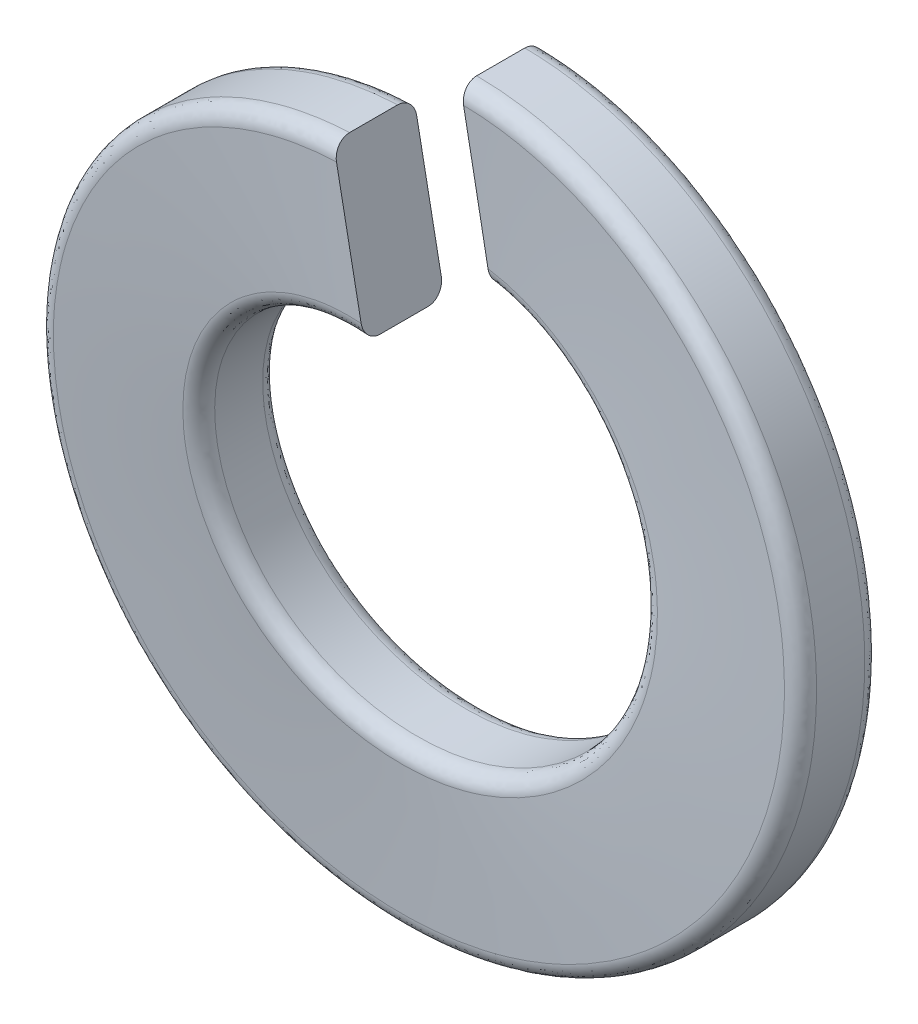
SolidWorks part; units mm, degrees
material "Plain Carbon Steel"
ref_plane "Front Plane" through (0, 0, 0) normal (0, 0, 1) x (1, 0, 0)
ref_plane "Top Plane" through (0, 0, 0) normal (0, 1, 0) x (1, 0, 0)
ref_plane "Right Plane" through (0, 0, 0) normal (1, 0, 0) x (0, 0, -1)
sketch "Sketch1" plane through (0, 0, 0) normal (0, 0, 1) x (1, 0, 0)
  line L0 (0, -2.2) -> (0, 2.2) construction
  line L1 (-0.096, 2.1979) -> (0.0978, 1.196) construction
  line L2 (0, 0) -> (-0.6, -1.0392) construction
  line L3 (0, 1.2) -> (-0.1917, 2.1916) construction
  line L4 (0, 0) -> (-0.1917, 2.1916) construction
  line L5 (-0.096, 2.1979) -> (0, 0) construction
  circle A0 centre (0, 0) radius 2.2 construction
  circle A1 centre (0, 0) radius 1.2 construction
  point P6 (0, -1.2)
  dimension "ID" = 2.4
  dimension "OD" = 4.4
  dimension "D2" = 5
  dimension "D1" = 30
  dimension "D3" = 2.5
sketch "Sketch2" plane through (0, 0, 0) normal (1, 0, 0) x (0, 0, -1)
  line L0 (-0.6, 0) -> (0.6, 0) construction
  line L1 (0, -2.2) -> (0, 2.2) construction
  line L2 (-0.6, 2.2) -> (-0.1, 2.2) construction
  line L3 (-0.6, 2.2) -> (-0.6, 1.2) construction
  line L4 (-0.6, 1.2) -> (-0.1, 1.2) construction
  line L5 (-0.1, 2.2) -> (-0.1, 1.2) construction
  line L6 (0, -2.2) -> (0, 2.2) construction
  line L12 (-0.25, -1.2) -> (0.25, -1.2) construction
  line L13 (-0.25, -1.2) -> (-0.25, -2.2) construction
  line L14 (-0.25, -2.2) -> (0.25, -2.2) construction
  line L15 (0.25, -1.2) -> (0.25, -2.2) construction
  point P8 (-0.35, 2.2)
  point P13 (0.25, -2.1)
  point P15 (0.6, 2.2)
  point P19 (0.35, 2.2)
  dimension "Thickness" = 0.5
  dimension "Helix Height" = 0.7
  dimension "Height" = 1.2
  dimension "Radius" = 0.1
ref_plane "Plane1" through (0, 0, 0.35) normal (0, 0, 1) x (1, 0, 0)
sketch "Sketch3" plane through (0, 0, 0.35) normal (0, 0, 1) x (1, 0, 0)
  circle A0 centre (0, 0) radius 2.2 construction
  circle A1 centre (0, 0) radius 2.2
curve "Helix/Spiral1" pitch 0.7007 height 0.7 turns 0.999
ref_plane "Plane2" through (0.2237, 0.0432, 0) normal (0.9818, 0.1898, 0) x (0.0066, -0.0343, -0.9994)
sketch "Sketch4" plane through (0.2511, -0.0988, 0.0051) normal (0.9818, 0.1898, 0) x (0.0066, -0.0343, -0.9994)
  line L0 (-0.6752, 2.2825) -> (-0.1755, 2.3) construction
  line L10 (-0.6408, 1.3013) -> (-0.1411, 1.3188) construction
  line L12 (-0.6762, 2.3107) -> (-0.1765, 2.3282)
  line L13 (-0.1765, 2.3282) -> (-0.1411, 1.3188)
  line L14 (-0.6408, 1.3013) -> (-0.1411, 1.3188)
  line L15 (-0.6762, 2.3107) -> (-0.6408, 1.3013)
sweep "Sweep1" add profiles "Sketch4" path "Helix/Spiral1"
sketch "Sketch5" plane through (0, 0, 0) normal (0, 0, 1) x (1, 0, 0)
  line L0 (0, 1.2) -> (-0.1917, 2.1916) construction
  line L1 (-0.096, 2.1979) -> (0.0978, 1.196) construction
  line L2 (0, 1.2) -> (-0.1917, 2.1916)
  line L3 (-0.096, 2.1979) -> (0.0978, 1.196)
  circle A0 centre (0, 0) radius 1.2 construction
  circle A1 centre (0, 0) radius 2.2 construction
  arc A2 (0.0978, 1.196) -> (0, 1.2) centre (0, 0) ccw
  arc A3 (-0.096, 2.1979) -> (-0.1917, 2.1916) centre (0, 0) ccw
extrude "Cut-Extrude1" cut sketch "Sketch5" against normal through all
fillet "Fillet1" radius 0.1 4 edges
equation "\"D3@Helix/Spiral1\"=\"Helix Height@Sketch2\""
equation "\"D7@Helix/Spiral1\"=90+\"D2@Sketch1\""
equation "\"D1@Fillet1\"=\"Radius@Sketch2\""
equation "\"D3@Sketch1\"=\"D2@Sketch1\"/2"
